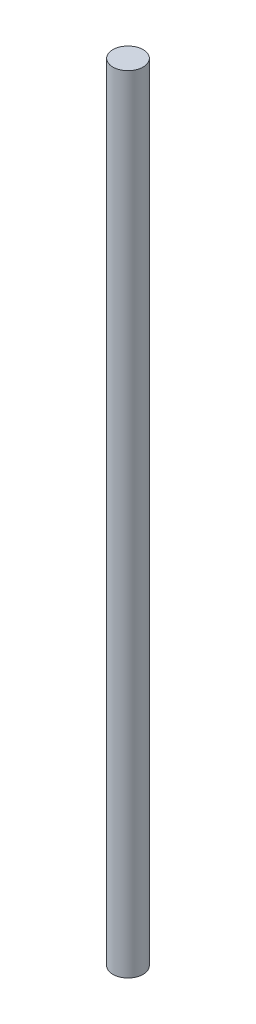
SolidWorks part; units mm, degrees
ref_plane "Front Plane" through (0, 0, 0) normal (0, 0, 1) x (1, 0, 0)
ref_plane "Top Plane" through (0, 0, 0) normal (0, 1, 0) x (1, 0, 0)
ref_plane "Right Plane" through (0, 0, 0) normal (1, 0, 0) x (0, 0, -1)
sketch "Sketch1" plane through (0, 0, 0) normal (0, 1, 0) x (1, 0, 0)
  circle A0 centre (0, 0) radius 4.7625
  dimension "D1" = 9.525
extrude "Boss-Extrude1" add sketch "Sketch1" along normal blind 247.65
equation "\"Lead_Screw_Diam\" = 0.375in"
equation "\"Mid_Coupler_Length\" = 8in"
equation "\"Lead_Screw_Length\" = \"Mid_Coupler_Length\" + 2*0.375in + 2*0.5in"
equation "\"D1@Sketch1\"=\"Lead_Screw_Diam\""
equation "\"D1@Boss-Extrude1\"=\"Lead_Screw_Length\""
